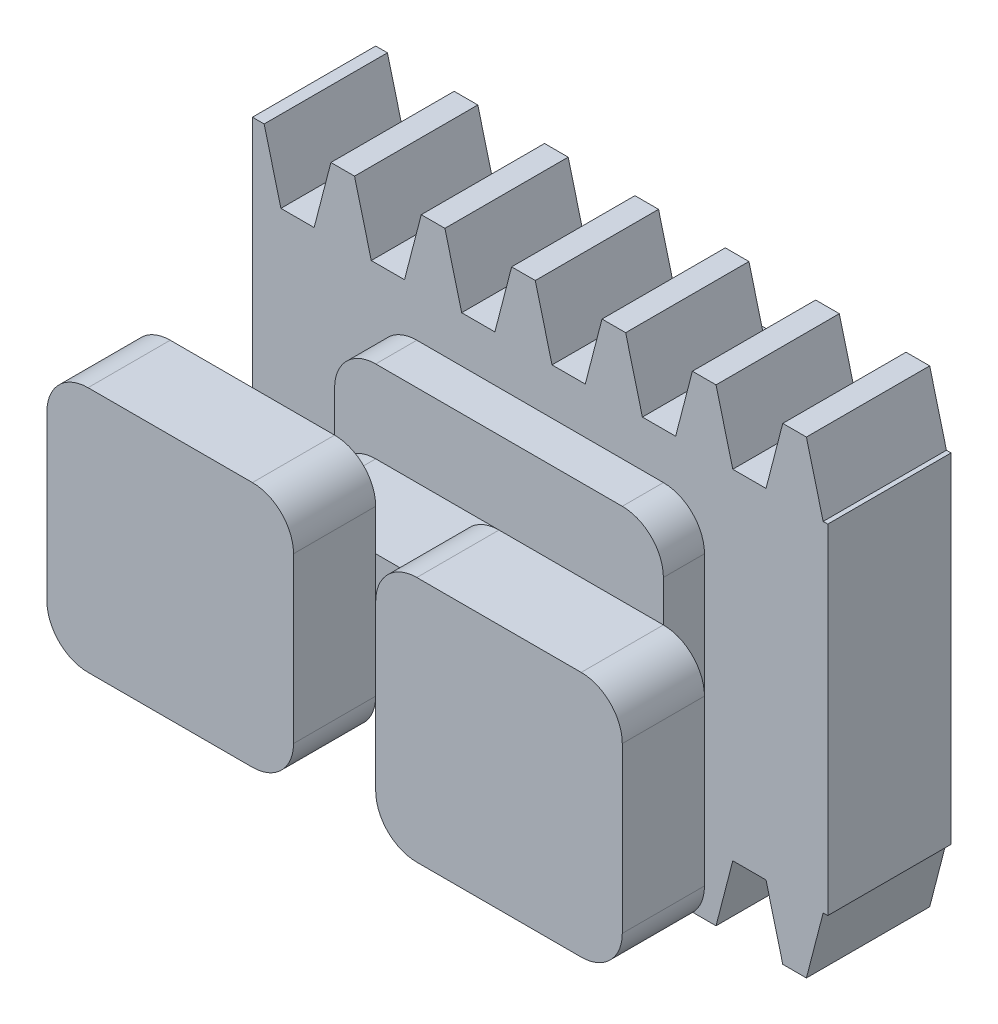
SolidWorks part; units mm, degrees
extrude "Blank" add sketch "BlankSke" against normal blind 3
sketch "BlankSke" plane through (0, 0, 0) normal (0, 0, 1) x (1, 0, 0)
  line L1 (0, 0) -> (25, 0)
  line L2 (0, 0) -> (0, 5.7)
  line L3 (0, 5.7) -> (25, 5.7)
  line L4 (25, 0) -> (25, 5.7)
  dimension "Length" = 25
ref_plane "Plane1" through (0, 0, 0) normal (0, 0, 1) x (1, 0, 0)
ref_plane "Plane2" through (0, 0, 0) normal (0, 1, 0) x (1, 0, 0)
ref_plane "Plane3" through (0, 0, 0) normal (1, 0, 0) x (0, 0, -1)
other "Configuration Table"
sketch "HoldingSke" plane through (0, 0, 0) normal (0, 1, 0) x (1, 0, 0)
  line L0 (0, 0) -> (0.1988, 1.4147)
  line L1 (-15, 0) -> (100, 0) construction
  line L2 (0, 0) -> (-2.1039, 2.3779)
  line L3 (0, 0) -> (-11.863, 4.5341)
  line L4 (0, 0) -> (8.4147, 1.9427)
  line L5 (0, 0) -> (-23.7986, -8.8762)
  line L6 (0, 0) -> (-10.5278, -7.1032)
  line L9 (-67.7845, 28.3722) -> (-43.5808, 34.6317)
  line L10 (-76.2, 3.0779) -> (-71.2, 3.0779)
  line L11 (0, 0) -> (-3, 0)
  line L12 (-76.2, 101.6) -> (-76.173, 101.6)
  line L13 (24.9733, 27.94) -> (52.9518, 28.4284)
  line L14 (24.9733, 27.94) -> (24.9743, 27.94)
  line L15 (24.9733, 27.94) -> (100.4006, 29.5858)
  circle A0 centre (0, 0) radius 19.05
  circle A1 centre (0, 0) radius 2.5
  circle A2 centre (0, 0) radius 12.7
  dimension "Num_teeth" = 13
  dimension "Width" = 3
  dimension "Length" = 25
  dimension "Pitch_height" = 5
sketch "TooCutSkeIll" plane through (0, 0, 0) normal (0, 0, 1) x (1, 0, 0)
  line L0 (-0.8064, 5.679) -> (-0.4386, 4.2569)
  line L1 (-0.2682, 4.125) -> (0.2682, 4.125)
  line L2 (0.4386, 4.2569) -> (0.8064, 5.679)
  line L3 (25, 5.7) -> (0, 5.7) construction
  line L4 (0, 0) -> (0, 64.897) construction
  line L5 (-13.208, 5) -> (12.954, 5) construction
  line L6 (0, 0) -> (25, 0) construction
  line L7 (0.6308, 5) -> (0.6308, 48.7463) construction
  line L8 (-0.6308, 5) -> (-0.6308, 48.7463) construction
  line L9 (0.8335, 5.7) -> (0.8335, 5.7254)
  line L10 (-0.8335, 5.7) -> (-0.8335, 5.7254)
  line L11 (-0.8335, 5.7254) -> (0.8335, 5.7254)
  arc A0 (0.2682, 4.125) -> (0.4386, 4.2569) centre (0.2682, 4.301) ccw
  arc A1 (-0.4386, 4.2569) -> (-0.2682, 4.125) centre (-0.2682, 4.301) ccw
  arc A2 (0.8335, 5.7) -> (0.8064, 5.679) centre (0.8335, 5.672) ccw
  arc A3 (-0.8064, 5.679) -> (-0.8335, 5.7) centre (-0.8335, 5.672) ccw
  dimension "Addendum_plus" = 0.7254
  dimension "Pitch_height" = 5
  dimension "Pressure_angle" = 14.5
  dimension "Gap_width" = 1.2616
  dimension "Dedendum" = 0.875
extrude "ToothCutIll" [suppressed] cut sketch "TooCutSkeIll" against normal through all
sketch "TooCutSkeSim" plane through (0, 0, 0) normal (0, 0, 1) x (1, 0, 0)
  line L0 (0.4045, 4.125) -> (-0.4045, 4.125)
  line L1 (0.8184, 5.7254) -> (0.4045, 4.125)
  line L2 (0, 17.4625) -> (0, 53.467) construction
  line L3 (0.8184, 5.7254) -> (-0.8184, 5.7254)
  line L6 (-0.8184, 5.7254) -> (-0.4045, 4.125)
  line L9 (-0.6308, 5) -> (0.6308, 5) construction
  line L10 (0, 0) -> (25, 0) construction
  line L11 (0.6308, 5) -> (0.6308, 53.467) construction
  line L12 (-0.6308, 5) -> (-0.6308, 53.467) construction
  dimension "Addendum_plus" = 0.7254
  dimension "Pitch_height" = 5
  dimension "Pressure_angle" = 14.5
  dimension "Gap_width" = 1.2616
  dimension "Dedendum" = 0.875
extrude "ToothCutSim" cut sketch "TooCutSkeSim" against normal through all
pattern_linear "TeethCuts" count 13 spacing 2.1991 along (1, 0, 0) of "ToothCutIll", "ToothCutSim"
mirror "镜向1" [suppressed]
mirror "镜向2" about plane through (0, 0, -3) normal (0, -1, 0) of "Blank", "ToothCutSim", "TeethCuts"
sketch "草图1" plane through (0, 0, 0) normal (-1, 0, 0) x (0, 0, 1)
  line L1 (0, 4.125) -> (0, -4.125) construction
  line L4 (-3, 0) -> (0, 0) construction
  line L5 (-3, 4.125) -> (-3, -4.125) construction
  line L7 (0, -3) -> (0, 3)
  line L8 (0, 3) -> (-2, 3.5)
  line L9 (-2, 3.5) -> (-2, -3.5)
  line L10 (0, -3) -> (-2, -3.5)
  point P11 (-2.5, 0)
  point P12 (-2, 0)
  dimension "D1" = 3
  dimension "D2" = 3.5
  dimension "D3" = 2
sketch "草图2" plane through (0, 0, -3) normal (0, 0, -1) x (-1, 0, 0)
  line L0 (0, 0) -> (-25, 0) construction
  line L1 (0, 4.125) -> (0, -4.125) construction
  line L2 (-25, -5.692) -> (-25, 5.692) construction
  circle A0 centre (-12.5, 0) radius 2
  dimension "D1" = 4
extrude "凸台-拉伸1" add sketch "草图2" along normal blind 2.5
sketch "草图3" plane through (0, 0, -5.5) normal (0, 0, -1) x (-1, 0, 0)
  circle A0 centre (-12.5, 0) radius 0.5
  dimension "D1" = 1
extrude "切除-拉伸3" cut sketch "草图3" against normal through all
sketch "草图4" plane through (0, 0, -3) normal (0, 0, -1) x (-1, 0, 0)
  line L0 (-12.5, 0) -> (-21.8848, 0) construction
  line L1 (-12.5, 0) -> (-2.5, 0) construction
  line L2 (-21.8848, 2.1496) -> (-21.8848, -2.1496)
  line L3 (-22.3956, 4.125) -> (-22.803, 5.7) construction
  line L4 (-2.5, 4.125) -> (-2.5, -4.125)
  line L6 (-1.7946, -4.125) -> (-2.6036, -4.125) construction
  line L7 (-22.3956, -4.125) -> (-22.803, -5.7) construction
  line L9 (-1.7946, 4.125) -> (-2.6036, 4.125) construction
  line L10 (-21.8848, 2.1496) -> (-21.8848, 5.9598)
  line L11 (-21.8848, 5.9598) -> (-25.6774, 5.9598)
  line L12 (-25.6774, 5.9598) -> (-25.6774, -6.5792)
  line L13 (-25.6774, -6.5792) -> (-21.8848, -6.5792)
  line L14 (-21.8848, -6.5792) -> (-21.8848, -2.1496)
  line L15 (-2.5, 4.125) -> (-2.5, 6.4022)
  line L16 (-2.5, 6.4022) -> (0, 6.4022)
  line L17 (0, 6.4022) -> (0, -6.0736)
  line L18 (0, -6.0736) -> (-2.5, -6.0736)
  line L19 (-2.5, -6.0736) -> (-2.5, -4.125)
  dimension "D2" = 10
extrude "切除-拉伸4" cut sketch "草图4" against normal blind 10
sketch "草图5" plane through (0, 0, 0) normal (0, 0, 1) x (1, 0, 0)
  line L0 (2.5, 2) -> (21.8848, 2)
  line L1 (2.5, 4.125) -> (2.5, -4.125) construction
  line L2 (21.8848, -4.125) -> (21.8848, 4.125) construction
  line L3 (21.8848, 2) -> (21.8848, -2)
  line L4 (21.8848, -2) -> (2.5, -2)
  line L5 (2.5, -2) -> (2.5, 2)
  point P8 (2.5, 0)
  point P9 (21.8848, 0)
  dimension "D1" = 4
sketch "草图6" plane through (0, 0, 0) normal (0, 0, 1) x (1, 0, 0)
  line L0 (1.1742, 0) -> (24.2349, 0) construction
  line L1 (8.5, 1) -> (8.5, -1)
  line L2 (8.5, -1) -> (16.5, -1)
  line L3 (16.5, -1) -> (16.5, 1)
  line L4 (16.5, 1) -> (8.5, 1)
  point P2 (16.5, 0)
  point P4 (12.5, 0)
  point P5 (8.5, 0)
  dimension "D1" = 2
  dimension "D2" = 8
  dimension "D3" = 4
extrude "凸台-拉伸3" add sketch "草图6" along normal blind 3
sketch "草图7" plane through (0, 0, 3) normal (0, 0, 1) x (1, 0, 0)
  line L0 (5.5, 3) -> (11.5, 3)
  line L1 (19.5, 3) -> (19.5, -3)
  line L2 (19.5, -3) -> (13.5, -3)
  line L3 (5.5, -3) -> (5.5, 3)
  line L5 (16.5, 1) -> (8.5, 1) construction
  line L6 (8.5, -1) -> (16.5, -1) construction
  line L7 (8.5, 1) -> (8.5, -1) construction
  line L8 (16.5, -1) -> (16.5, 1) construction
  line L9 (11.5, 3) -> (11.5, -3)
  line L10 (13.5, 3) -> (13.5, -3)
  line L11 (13.5, 3) -> (19.5, 3)
  line L12 (11.5, -3) -> (5.5, -3)
  dimension "D1" = 2
  dimension "D2" = 2
  dimension "D3" = 3
  dimension "D4" = 3
  dimension "D5" = 6
  dimension "D6" = 6
extrude "凸台-拉伸4" add sketch "草图7" along normal blind 2
fillet "圆角1" radius 1 4 edges at (16.5, -1, 1.5) (8.5, -1, 1.5) (16.5, 1, 1.5) (8.5, 1, 1.5)
fillet "圆角2" radius 1 8 edges at (5.5, -3, 4) (5.5, 3, 4) (11.5, 3, 4) (11.5, -3, 4) (13.5, -3, 4) (13.5, 3, 4) (19.5, 3, 4) (19.5, -3, 4)
sketch "草图8" plane through (0, 0, 0) normal (0, 0, 1) x (1, 0, 0)
  line L15 (8.5, 3) -> (8.5, -3)
  line L16 (10.5, 3) -> (6.5, 3) construction
  line L17 (6.5, -3) -> (10.5, -3) construction
  line L18 (8.5, -3) -> (16.5, -3)
  line L19 (14.5, -3) -> (18.5, -3) construction
  line L20 (16.5, -3) -> (16.5, 3)
  line L21 (16.5, 3) -> (8.5, 3)
  line L22 (11.5, -2) -> (11.5, 2) construction
  dimension "D1" = 3
  dimension "D2" = 8
extrude "凸台-拉伸5" add sketch "草图8" along normal blind 1
fillet "圆角5" radius 1 4 edges at (16.5, -3, 0.5) (8.5, -3, 0.5) (8.5, 3, 0.5) (16.5, 3, 0.5)
sketch "草图9" plane through (0, 0, 0) normal (0, 0, 1) x (1, 0, 0)
  line L0 (5.5, 0) -> (5.5, -6.2232)
  line L1 (5.5, 2) -> (5.5, -2) construction
  line L2 (5.5, -6.2232) -> (2.2382, -6.2232)
  line L3 (2.2382, -6.2232) -> (2.2382, 6.2496)
  line L4 (2.2382, 6.2496) -> (5.5, 6.2496)
  line L5 (5.5, 6.2496) -> (5.5, 0)
  line L6 (19.5, 0) -> (19.5, -6.2232)
  line L7 (19.5, -2) -> (19.5, 2) construction
  line L8 (19.5, -6.2232) -> (22.4063, -6.2232)
  line L9 (22.4063, -6.2232) -> (22.4063, 6.2496)
  line L10 (22.4063, 6.2496) -> (19.5, 6.2496)
  line L11 (19.5, 6.2496) -> (19.5, 0)
extrude "切除-拉伸5" cut sketch "草图9" against normal through all
sketch "草图10" plane through (0, 0, -5.5) normal (0, 0, -1) x (-1, 0, 0)
  circle A0 centre (-12.5, 0) radius 1
extrude "切除-拉伸6" cut sketch "草图10" against normal blind 5.5
equation "' \"Module@HoldingSke\" = 6.35"
equation "' \"Num_teeth@HoldingSke\" = 12"
equation "' \"Ap@HoldingSke\" =  20"
equation "' \"Ap@HoldingSke\" = 20"
equation "' \"Width@HoldingSke\" = 0.25 * 25.4"
equation "' \"Show_teeth@HoldingSke\" = 500"
equation "' \"Backlash@HoldingSke\" = 0.009 * 25.4"
equation "' \"Addendum_fac@HoldingSke\" = 1.0"
equation "' \"Dedendum_fac@HoldingSke\" = 1.25"
equation "' \"Dedendum_add@HoldingSke\" = 0.00005 * 25.4"
equation "' \"Clearance_fac@HoldingSke\" = 0.25"
equation "' \"Pitch_height@HoldingSke\" = 1 * 25.4"
equation "' \"Length@HoldingSke\" = 4.71 * 25.4"
equation "\"Pitch@HoldingSke\" = 1 / \"Module@HoldingSke\""
equation "\"MPH@HoldingSke\" = \"Dedendum_fac@HoldingSke\" / \"Pitch@HoldingSke\" + 2 * \"Dedendum_add@HoldingSke\" + 0.002 * 25.4"
equation "\"MPH@HoldingSke\" = ((sgn( \"MPH@HoldingSke\" - \"Pitch_height@HoldingSke\")+1)*( \"MPH@HoldingSke\" - \"Pitch_height@HoldingSke\"))/2 + \"Pitch_height@HoldingSke\""
equation "\"Blank_height@BlankSke\" = \"Pitch_height@HoldingSke\" + \"Addendum_fac@HoldingSke\"  / \"Pitch@HoldingSke\" "
equation "\"Length@BlankSke\" =  \"Length@HoldingSke\""
equation "\"Face_width@Blank\" = \"Width@HoldingSke\""
equation "\"Pressure_angle@TooCutSkeIll\" = \"Ap@HoldingSke\""
equation "\"Addendum_plus@TooCutSkeIll\" =  \"Addendum_fac@HoldingSke\"  / \"Pitch@HoldingSke\" + 0.001 *25.4"
equation "\"Dedendum@TooCutSkeIll\" = \"Dedendum_fac@HoldingSke\"  / \"Pitch@HoldingSke\""
equation "\"Pitch_height@TooCutSkeIll\" =  \"MPH@HoldingSke\""
equation "\"Gap_width@TooCutSkeIll\" = 3.14159265 / 2 / \"Pitch@HoldingSke\" + 6 * \"Backlash@HoldingSke\""
equation "\"Pressure_angle@TooCutSkeSim\" = \"Ap@HoldingSke\""
equation "\"Addendum_plus@TooCutSkeSim\" =  \"Addendum_fac@HoldingSke\"  / \"Pitch@HoldingSke\" + 0.001 * 25.4"
equation "\"Dedendum@TooCutSkeSim\" = \"Dedendum_fac@HoldingSke\"  / \"Pitch@HoldingSke\""
equation "\"Pitch_height@TooCutSkeSim\" =  \"MPH@HoldingSke\""
equation "\"Gap_width@TooCutSkeSim\" = 3.14159265 / 2 / \"Pitch@HoldingSke\" + 6 * \"Backlash@HoldingSke\""
equation "\"Root_fillet@TooCutSkeIll\" = \"Clearance_fac@HoldingSke\" / \"Pitch@HoldingSke\" + \"Dedendum_add@HoldingSke\""
equation "\"Break_rad@TooCutSkeIll\" = 0.02 / \"Pitch@HoldingSke\" * 2"
equation "\"Linear_pitch@TeethCuts\" = 3.14159265 / \"Pitch@HoldingSke\""
equation "\"Num_teeth@HoldingSke\" = int( ( \"Length@HoldingSke\" + 0 ) / (3.14159265 / \"Pitch@HoldingSke\")) + 0.9999  + 1"
equation " \"Num_teeth@TeethCuts\" = int( \"Show_teeth@HoldingSke\" ) + 1"
equation " \"Num_teeth@TeethCuts\" = ((sgn( \"Num_teeth@TeethCuts\" - \"Num_teeth@HoldingSke\" )-1)*( \"Num_teeth@TeethCuts\" - \"Num_teeth@HoldingSke\" ))/-2+ \"Num_teeth@HoldingSke\""
equation " \"Num_teeth@TeethCuts\" = ((sgn( \"Num_teeth@TeethCuts\" - 2.0)+1)*( \"Num_teeth@TeethCuts\" - 2.0))/2 +2.0"
